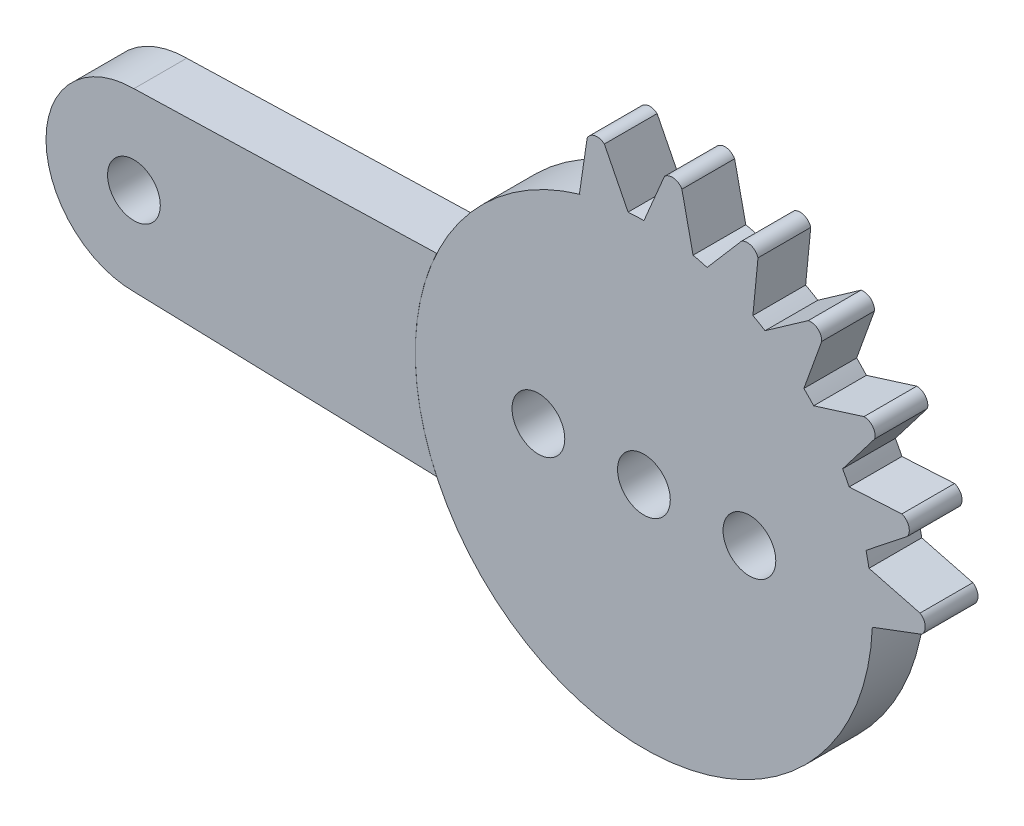
SolidWorks part; units mm, degrees
ref_plane "Piano frontale" through (0, 0, 0) normal (0, 0, 1) x (1, 0, 0)
ref_plane "Piano superiore" through (0, 0, 0) normal (0, 1, 0) x (1, 0, 0)
ref_plane "Piano destro" through (0, 0, 0) normal (1, 0, 0) x (0, 0, -1)
sketch "Schizzo1" plane through (0, 0, 0) normal (0, 0, 1) x (1, 0, 0)
  line L0 (-13, 0) -> (13, 0) construction
  circle A0 centre (0, 0) radius 13
  circle A1 centre (-6, 0) radius 1.5
  circle A2 centre (6, 0) radius 1.5
  circle A3 centre (0, 0) radius 1.5
  point P10 (0, 0)
  dimension "D1" = 26
  dimension "D4" = 3
  dimension "D5" = 3
  dimension "D6" = 3
  dimension "D2" = 6
  dimension "D3" = 6
sketch "Schizzo2" plane through (0, 0, 0) normal (0, 0, 1) x (1, 0, 0)
  line L0 (-6, 0) -> (-29, 0) construction
  line L1 (-29, 5) -> (-29, -5) construction
  line L6 (-29, 5) -> (-11.7792, 5.5)
  line L7 (-29, -5) -> (-11.7792, -5.5)
  circle A0 centre (-29, 0) radius 1.5
  arc A1 (-29, 5) -> (-29, -5) centre (-29, 0) ccw
  circle A2 centre (0, 0) radius 13 construction
  circle A3 centre (0, 0) radius 13.0045
  point P5 (-29, 5)
  point P8 (-29, -5)
  dimension "D2" = 3
  dimension "D4" = 10
  dimension "D3" = 11
  dimension "D5" = 26.009
  dimension "D1" = 23
sketch "Schizzo3" plane through (0, 0, 0) normal (0, 0, 1) x (1, 0, 0)
  line L0 (0, 13) -> (0, 0) construction
  line L1 (0, 0) -> (13, 0) construction
  line L2 (1.3976, 12.848) -> (0.8347, 12.9092) construction
  line L3 (0, -9.0597) -> (0, 9.0597) construction
  line L4 (1.3976, 12.848) -> (1.8006, 12.8041) construction
  line L5 (0, 13) -> (2.7952, 12.6959) construction
  line L6 (2.7952, 12.6959) -> (1.3976, 12.848) construction
  line L7 (0, 13) -> (-0.8685, 12.971) construction
  line L8 (-0.4495, 12.985) -> (-0.5424, 15.7635) construction
  line L9 (1.1676, 15.7635) -> (0, 13)
  line L10 (2.1601, 15.6279) -> (2.7952, 12.6959)
  line L11 (-3.2297, 15.4477) -> (-3.6676, 12.4798)
  line L12 (-2.2485, 15.6492) -> (-0.8989, 12.9699)
  line L13 (2.7952, 12.6959) -> (3.5952, 12.493) construction
  line L14 (3.1641, 12.6023) -> (3.1952, 12.5945) construction
  line L15 (3.1952, 12.5945) -> (3.5748, 14.0909) construction
  line L16 (5.5513, 14.7676) -> (3.5952, 12.493)
  line L17 (6.4883, 14.4136) -> (6.1973, 11.4277)
  line L18 (6.1973, 11.4277) -> (6.8885, 11.0249) construction
  line L19 (6.5429, 11.2263) -> (7.3923, 12.6837) construction
  line L20 (9.343, 12.7498) -> (6.8885, 11.0249)
  line L21 (10.1129, 12.109) -> (9.0979, 9.2859)
  line L22 (9.0979, 9.2859) -> (9.6518, 8.7087) construction
  line L23 (9.3749, 8.9973) -> (10.5474, 10.1226) construction
  line L24 (13.1229, 8.8113) -> (11.2986, 6.4297)
  line L25 (12.5142, 9.6069) -> (9.6518, 8.7087)
  line L26 (11.2986, 6.4297) -> (11.6727, 5.7226) construction
  line L27 (11.4857, 6.0762) -> (12.5229, 6.6249) construction
  line L28 (14.668, 5.8907) -> (11.6727, 5.7226)
  line L29 (14.9832, 4.9399) -> (12.6301, 3.0789)
  line L30 (12.6301, 3.0789) -> (12.7987, 2.2789) construction
  line L31 (12.7144, 2.6789) -> (14.1522, 2.9819) construction
  line L32 (15.7026, 1.5256) -> (12.7987, 2.2789)
  line L33 (15.7978, 0.5285) -> (12.9893, -0.5263)
  line L34 (-3.6676, 12.4798) -> (-0.8989, 12.9699) construction
  line L35 (-3.6676, 12.4798) -> (-0.8989, 12.9699)
  circle A0 centre (0, 0) radius 13 construction
  arc A1 (1.1676, 15.7635) -> (2.1601, 15.6279) centre (1.6117, 15.314) cw
  arc A2 (-2.2485, 15.6492) -> (-3.2297, 15.4477) centre (-2.6616, 15.1711) ccw
  arc A3 (6.4883, 14.4136) -> (5.5513, 14.7676) centre (5.8837, 14.2303) ccw
  arc A4 (9.343, 12.7498) -> (10.1129, 12.109) centre (9.4815, 12.1334) cw
  arc A5 (13.1229, 8.8113) -> (12.5142, 9.6069) centre (12.5126, 8.975) ccw
  arc A6 (14.668, 5.8907) -> (14.9832, 4.9399) centre (14.46, 5.2941) cw
  arc A7 (15.7978, 0.5285) -> (15.7026, 1.5256) centre (15.3667, 0.9904) ccw
  circle A8 centre (0, 0) radius 13
  point P13 (2.7952, 12.6959)
  dimension "D8" = 0.8685
  dimension "D18" = 3
  dimension "D20" = 26
  dimension "D15" = 0.6318
  dimension "D1" = 2.4753
  dimension "D2" = 1.0017
  dimension "D3" = 2.8732
  dimension "D4" = 3
  dimension "D5" = 3
  dimension "D6" = 2.8117
  dimension "D7" = 2.82
  dimension "D9" = 0.8
  dimension "D10" = 0.8
  dimension "D11" = 0.8253
  dimension "D12" = 0.8
  dimension "D13" = 0.8
  dimension "D14" = 0.8
  dimension "D16" = 3
  dimension "D17" = 2.7229
  dimension "D19" = 2.8418
extrude "Estrusione-Estrusione2" add sketch "Schizzo1" along normal blind 3
extrude "Estrusione-Estrusione4" add sketch "Schizzo2" along normal blind 3 contours A3 L6 A1 L7 A0 region at (-22.3986, 0, 0)
extrude "Estrusione-Estrusione5" add sketch "Schizzo3" along normal blind 3 contours A8 L35 L12 A2 L11 | A8 L10 A1 L9 | A8 L17 A3 L16 | A8 L21 A4 L20 | A8 L24 A5 L25 | A8 L29 A6 L28 | A8 L33 A7 L32 region at (1.5155, 14.1322, 0) region at (-2.487, 13.9955, 0) region at (5.4048, 13.1455, 0) region at (14.1819, 0.9422, 0) region at (8.7737, 11.182, 0) region at (11.533, 8.3069, 0) region at (13.3564, 4.8602, 0)
